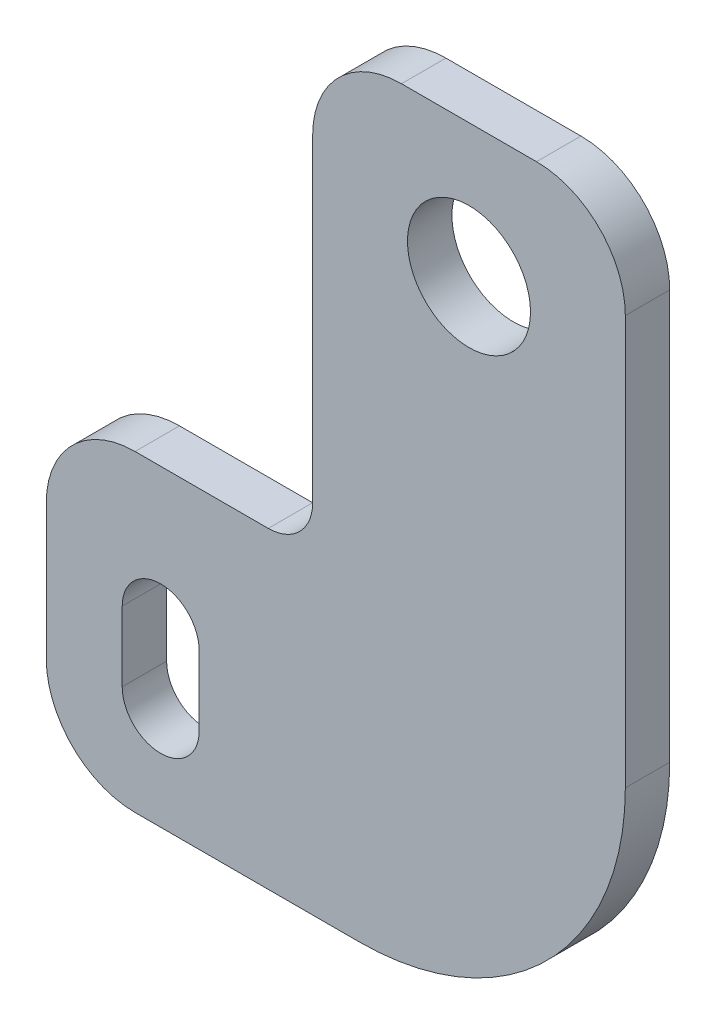
SolidWorks part; units mm, degrees
material "Custom Plastic"
ref_plane "X-Y Datum" through (0, 0, 0) normal (0, 0, 1) x (1, 0, 0)
ref_plane "X-Z Datum" through (0, 0, 0) normal (0, 1, 0) x (1, 0, 0)
ref_plane "Y-Z Datum" through (0, 0, 0) normal (1, 0, 0) x (0, 0, -1)
sketch "Sketch1" plane through (0, 0, 0) normal (0, 0, 1) x (1, 0, 0)
  line L1 (0, 0) -> (41.3978, 0)
  line L2 (0, 0) -> (0, 22.352)
  line L3 (0, 22.352) -> (19.0458, 22.352)
  line L5 (19.0458, 54.644) -> (41.3978, 54.644)
  line L6 (19.0458, 54.644) -> (19.0458, 22.352)
  line L7 (41.3978, 54.644) -> (41.3978, 0)
  point P3 (30.2218, 54.644)
  point P12 (30.2218, 45.119)
  dimension "D1" = 9.525
  dimension "D2" = 22.352
  dimension "D3" = 22.352
base flange "Base-Flange1" sketch "Sketch1" thickness 3.175 reverse thickness direction no parameters "D1"=1.5875
fillet "Fillet1" radius 6.35 4 edges at (0, 0, -1.5875) (0, 22.352, -1.5875) (19.0458, 54.644, -1.5875) (41.3978, 54.644, -1.5875)
fillet "Fillet2" radius 19.05 1 edges at (41.3978, 0, -1.5875)
fillet "Fillet3" radius 3.175 1 edges at (19.0458, 22.352, -1.5875)
sketch "Sketch3" plane through (0, 0, 0) normal (0, 0, 1) x (1, 0, 0)
  line L0 (10.9309, 12.325) -> (10.9309, 7.325) construction
  line L1 (5.4309, 7.325) -> (5.4309, 12.325) construction
  line L2 (10.9309, 12.325) -> (10.9309, 7.325)
  line L3 (5.4309, 7.325) -> (5.4309, 12.325)
  line L4 (35.0478, 54.644) -> (25.3958, 54.644) construction
  arc A3 (10.9309, 12.325) -> (5.4309, 12.325) centre (8.1809, 12.325) ccw construction
  arc A4 (5.4309, 7.325) -> (10.9309, 7.325) centre (8.1809, 7.325) ccw construction
  arc A5 (10.9309, 12.325) -> (5.4309, 12.325) centre (8.1809, 12.325) ccw
  arc A6 (5.4309, 7.325) -> (10.9309, 7.325) centre (8.1809, 7.325) ccw
  circle A9 centre (30.2218, 45.119) radius 4.3969
  circle A10 centre (30.2218, 45.119) radius 4.3969
  dimension "D3" = 8.7938
  dimension "D2" = 9.525
  dimension "D1" = 0.3969
extrude "Cut-Extrude1" cut sketch "Sketch3" against normal blind 3.175 normal cut yes
sketch "Bend-Lines1" [suppressed] plane through (0, 0, 0) normal (0, 1, 0) x (1, 0, 0)
sketch "Bounding-Box1" [suppressed] plane through (0, 0, 0) normal (0, 1, 0) x (1, 0, 0)
sheet metal parameters "Sheet-Metal1" thickness 3.175 parameters "D1"=1.5875
flat pattern "Flat-Pattern1" [suppressed]
sketch "Bend-Lines2" plane through (0, 0, 0) normal (0, 1, 0) x (1, 0, 0)
sketch3d "Bounding-Box2" [suppressed]
  line L0 (41.5808, 0, 0) -> (41.5808, 54.644, 0) construction
  line L1 (0, 0, 0) -> (0, 54.644, 0) construction
  line L2 (41.5808, 0, 0) -> (0, 0, 0) construction
  line L3 (41.5808, 54.644, 0) -> (0, 54.644, 0) construction
sheet metal parameters "Sheet-Metal3" thickness 3.175 parameters "D1"=1.5875
flat pattern "Flat-Pattern1"
sketch "Bend-Lines2" plane through (0, 0, 0) normal (0, 1, 0) x (1, 0, 0)
sketch3d "Bounding-Box2" [suppressed]
  line L0 (41.3978, 54.644, 0) -> (41.3978, 0, 0) construction
  line L1 (0, 54.644, 0) -> (0, 0, 0) construction
  line L2 (41.3978, 54.644, 0) -> (0, 54.644, 0) construction
  line L3 (41.3978, 0, 0) -> (0, 0, 0) construction
